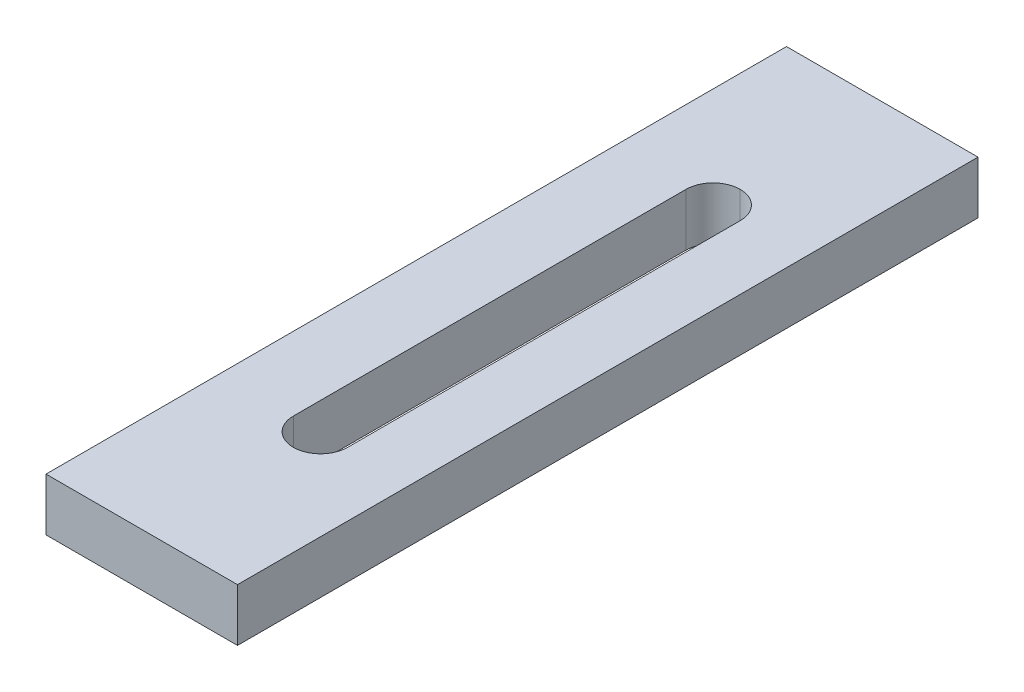
SolidWorks part; units mm, degrees
material "PVC hart"
ref_plane "Ebene vorne" through (0, 0, 0) normal (0, 0, 1) x (1, 0, 0)
ref_plane "Ebene oben" through (0, 0, 0) normal (0, 1, 0) x (1, 0, 0)
ref_plane "Ebene rechts" through (0, 0, 0) normal (1, 0, 0) x (0, 0, -1)
sketch "Skizze1" plane through (0, 0, 0) normal (0, 1, 0) x (1, 0, 0)
  line L0 (-3, 11.6) -> (3, 11.6)
  line L1 (0, 11.6) -> (0, -11.6) construction
  line L2 (1, 0) -> (3, 0) construction
  line L3 (3, -11.6) -> (3, 11.6)
  line L5 (-0.7, 7) -> (1, 7)
  line L6 (-0.7, 7) -> (-0.7, -7)
  line L7 (-0.7, -7) -> (1, -7)
  line L9 (1, 7) -> (1, -7)
  line L11 (-3, -11.6) -> (-3, 11.6)
  line L27 (-3, -11.6) -> (3, -11.6)
  dimension "D5" = 2
  dimension "D3" = 14
  dimension "D1" = 1.7
  dimension "D2" = 6
  dimension "D4" = 23.2
extrude "Aufsatz-Linear austragen1" add sketch "Skizze1" against normal mid plane 1.65 contours L11 L27 L0 region at (0, 0, -11.3604)
fillet "Verrundung2" radius 0.85 4 edges at (-0.7, 0, 7) (1, 0, 7) (1, 0, -7) (-0.7, 0, -7)
